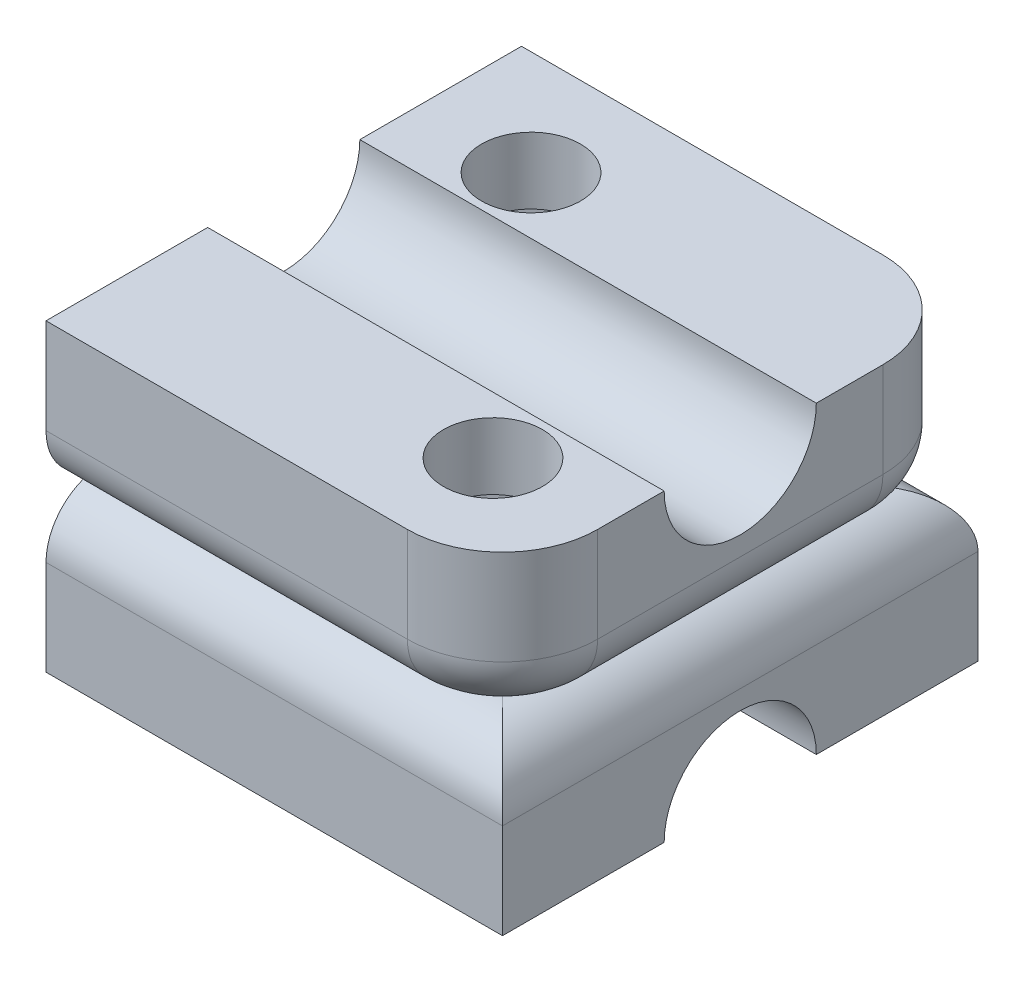
SolidWorks part; units mm, degrees
ref_plane "Front Plane" through (0, 0, 0) normal (0, 0, 1) x (1, 0, 0)
ref_plane "Top Plane" through (0, 0, 0) normal (0, 1, 0) x (1, 0, 0)
ref_plane "Right Plane" through (0, 0, 0) normal (1, 0, 0) x (0, 0, -1)
sketch "Sketch1" plane through (0, 0, 0) normal (0, 1, 0) x (1, 0, 0)
  line L1 (-12, 12.5) -> (12, 12.5)
  line L2 (-12, 12.5) -> (-12, -12.5)
  line L3 (-12, -12.5) -> (12, -12.5)
  line L4 (12, 12.5) -> (12, -12.5)
  line L5 (-12, 12.5) -> (12, -12.5) construction
  line L6 (-12, -12.5) -> (12, 12.5) construction
  point P0 (0, 0)
  dimension "D1" = 25
  dimension "D2" = 24
extrude "Boss-Extrude1" add sketch "Sketch1" along normal blind 8
sketch "Sketch2" plane through (-12, 0, 0) normal (-1, 0, 0) x (0, 0, 1)
  circle A0 centre (0, 0) radius 4
  dimension "D1" = 8
extrude "Cut-Extrude1" cut sketch "Sketch2" against normal through all
sketch "Sketch3" plane through (0, 0, 0) normal (0, -1, 0) x (1, 0, 0)
  line L0 (-6, -7) -> (6, 7) construction
  line L1 (-6, -7) -> (12.0808, -7) construction
  circle A0 centre (-6, -7) radius 2.6
  circle A1 centre (6, 7) radius 2.6
extrude "Cut-Extrude2" cut sketch "Sketch3" against normal through all
fillet "Fillet1" radius 3 3 edges at (0, 8, -12.5) (12, 8, 0) (0, 8, 12.5)
mirror "Mirror1" about plane through (0, 8, 0) normal (0, 1, 0) of bodies 103
fillet "Fillet2" radius 5 4 edges at (11.1213, 8.8787, 11.6213) (11.1213, 8.8787, -11.6213) (12, 13.5, -12.5) (12, 13.5, 12.5)
sketch "Sketch4" plane through (0, 8, 0) normal (0, -1, 0) x (1, 0, 0)
  line L1 (-6, -2.2657) -> (-10.1, -4.6329)
  line L2 (-10.1, -4.6329) -> (-10.1, -9.3671)
  line L3 (-10.1, -9.3671) -> (-6, -11.7343)
  line L4 (-6, -11.7343) -> (-1.9, -9.3671)
  line L5 (-1.9, -9.3671) -> (-1.9, -4.6329)
  line L6 (-1.9, -4.6329) -> (-6, -2.2657)
  line L7 (6, 2.2657) -> (10.1, 4.6329)
  line L8 (10.1, 4.6329) -> (10.1, 9.3671)
  line L9 (10.1, 9.3671) -> (6, 11.7343)
  line L10 (6, 11.7343) -> (1.9, 9.3671)
  line L11 (1.9, 9.3671) -> (1.9, 4.6329)
  line L12 (1.9, 4.6329) -> (6, 2.2657)
  circle A0 centre (-6, -7) radius 4.1 construction
  circle A1 centre (6, 7) radius 4.1 construction
  dimension "D1" = 8.2
extrude "Cut-Extrude3" cut sketch "Sketch4" against normal blind 4.5
